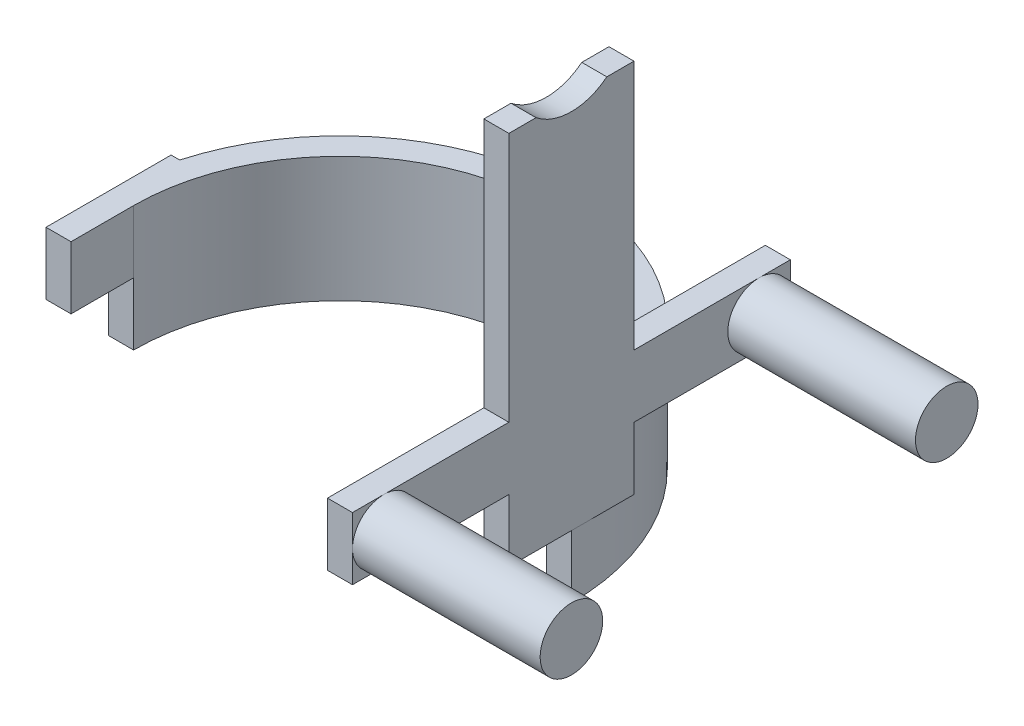
SolidWorks part; units mm, degrees
ref_plane "Front" through (0, 0, 0) normal (0, 0, 1) x (1, 0, 0)
ref_plane "Top" through (0, 0, 0) normal (0, 1, 0) x (1, 0, 0)
ref_plane "Right" through (0, 0, 0) normal (1, 0, 0) x (0, 0, -1)
sketch "草图1" plane through (0, 0, 0) normal (0, 1, 0) x (1, 0, 0)
  line L0 (-72.3418, 0) -> (74, 0) construction
  line L1 (0, 74) -> (0, -74) construction
  line L3 (-74, 20) -> (-71.2461, 20)
  line L4 (-74, 20) -> (-74, -20)
  line L5 (-74, -20) -> (-66, -20)
  line L6 (-66, 0) -> (-66, -20)
  line L7 (74, 20) -> (71.2461, 20)
  line L8 (74, 20) -> (74, -20)
  line L9 (74, -20) -> (66, -20)
  line L10 (66, 0) -> (66, -20)
  arc A0 (71.2461, 20) -> (-71.2461, 20) centre (0, 0) ccw
  arc A1 (66, 0) -> (-66, 0) centre (0, 0) ccw
  dimension "D1" = 40
  dimension "D2" = 20
  dimension "D3" = 8
  dimension "D4" = 8
  dimension "D6" = 40
  dimension "D7" = 20
extrude "凸台-拉伸1" add sketch "草图1" along normal blind 40
sketch "草图2" plane through (0, 40, 0) normal (0, 1, 0) x (1, 0, 0)
  line L1 (-74, -20) -> (-66, -20)
  line L2 (-74, -20) -> (-74, 20)
  line L3 (-74, 20) -> (-66, 20)
  line L4 (-66, -20) -> (-66, 20)
  line L5 (66, -20) -> (74, -20)
  line L6 (66, -20) -> (66, 20)
  line L7 (66, 20) -> (74, 20)
  line L8 (74, -20) -> (74, 20)
  dimension "D1" = 8
extrude "凸台-拉伸2" add sketch "草图2" along normal blind 100
sketch "草图3" plane through (-74, 0, 0) normal (-1, 0, 0) x (0, 0, 1)
  line L0 (-20, 140) -> (20, 140) construction
  circle A0 centre (0, 154) radius 18
  dimension "D1" = 14
extrude "切除-拉伸1" cut sketch "草图3" against normal through all
sketch "草图4" plane through (-74, 0, 0) normal (-1, 0, 0) x (0, 0, 1)
  line L1 (-20, 40) -> (29.7839, 40)
  line L2 (-20, 40) -> (-20, 153.9823)
  line L3 (-20, 153.9823) -> (29.7839, 153.9823)
  line L4 (29.7839, 40) -> (29.7839, 153.9823)
extrude "切除-拉伸3" cut sketch "草图4" against normal blind 10
sketch "草图5" plane through (0, 0, 0) normal (0, -1, 0) x (1, 0, 0)
  line L0 (66, 0) -> (66, 20) construction
  line L1 (-71.2461, 20) -> (-66, 20)
  line L3 (-74, 0) -> (-66, 0)
  line L4 (-66, 20) -> (-66, 0)
  line L5 (71.2461, 20) -> (66, 20)
  line L7 (74, 0) -> (66, 0)
  line L8 (66, 20) -> (66, 0)
  arc A0 (-66, 0) -> (66, 0) centre (0, 0) ccw construction
  arc A1 (-74, 0) -> (74, 0) centre (0, 0) ccw
  circle A2 centre (0, 0) radius 84.7622
  arc A3 (71.2461, 20) -> (-71.2461, 20) centre (0, 0) ccw
extrude "切除-拉伸4" cut sketch "草图5" against normal blind 20
sketch "草图6" plane through (74, 0, 0) normal (1, 0, 0) x (0, 0, -1)
  line L0 (66, 40) -> (0, 40) construction
  line L1 (70, 40) -> (-70, 40)
  line L2 (70, 40) -> (70, 60)
  line L3 (70, 60) -> (-70, 60)
  line L4 (-70, 40) -> (-70, 60)
  line L5 (0, 0) -> (0, 148.7503) construction
  dimension "D1" = 140
  dimension "D2" = 70
  dimension "D3" = 20
extrude "凸台-拉伸3" add sketch "草图6" against normal blind 8
sketch "草图7" plane through (74, 0, 0) normal (1, 0, 0) x (0, 0, -1)
  circle A0 centre (-60, 50) radius 10
  circle A1 centre (60, 50) radius 10
extrude "凸台-拉伸4" add sketch "草图7" along normal blind 60
